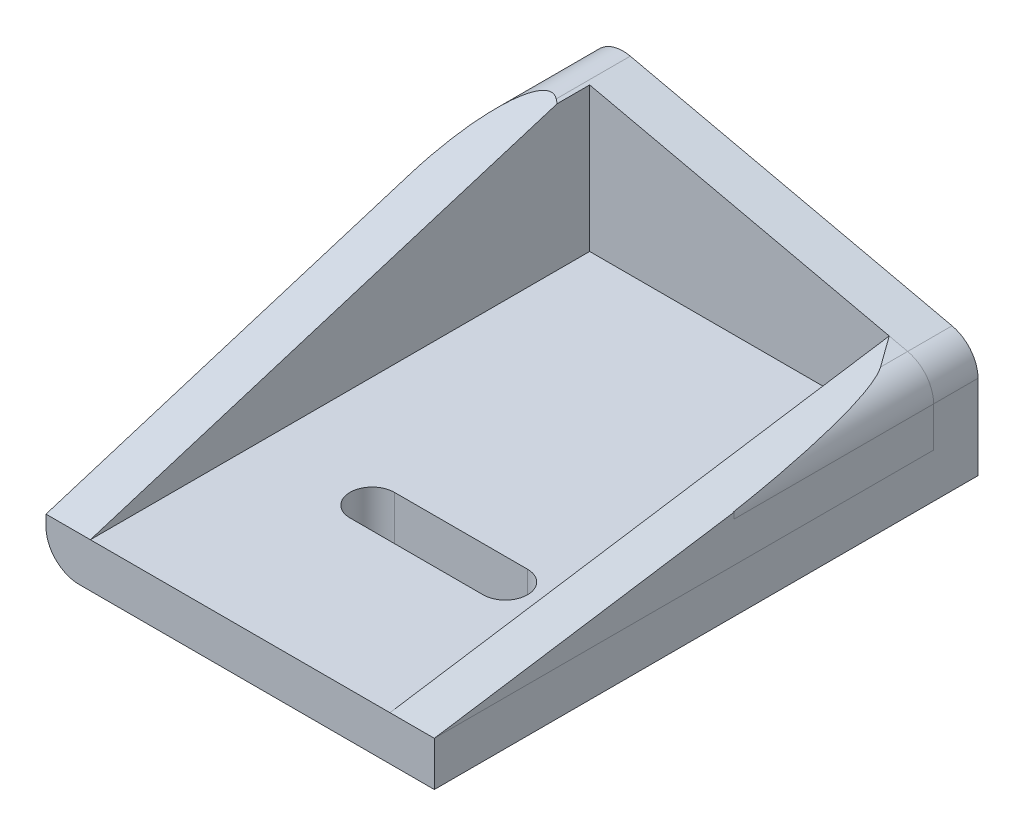
SolidWorks part; units mm, degrees
ref_plane "Front Plane" through (0, 0, 0) normal (0, 0, 1) x (1, 0, 0)
ref_plane "Top Plane" through (0, 0, 0) normal (0, 1, 0) x (1, 0, 0)
ref_plane "Right Plane" through (0, 0, 0) normal (1, 0, 0) x (0, 0, -1)
sketch "Sketch1" plane through (0, 0, 0) normal (0, 0, 1) x (1, 0, 0)
  line L1 (-155, 3) -> (-155, 7.6019) construction
  line L2 (-6, 0) -> (-152, 0) construction
  line L4 (-155, 3) -> (-155, 7.6019)
  line L5 (-120, 0) -> (-152, 0)
  line L6 (-120, 0) -> (-120, 10.5282)
  line L7 (-152, 0) -> (-155, 0)
  line L8 (-155, 0) -> (-155, 3)
  line L9 (-155, 7.6019) -> (-155, 10.5282)
  line L11 (-155, 10.5282) -> (-155, 17.9032)
  line L12 (-122.3392, 10.5282) -> (-271.3392, 44.1734) construction
  line L13 (-155, 17.9032) -> (-122.3392, 10.5282)
  line L14 (-122.3392, 10.5282) -> (-120, 10.5282)
  point P8 (-155, 5.3009)
  dimension "D1" = 35
extrude "Boss-Extrude2" add sketch "Sketch1" along normal blind 4
ref_plane "Plane2" through (-151, 0, 0) normal (-1, 0, 0) x (0, 0, 1)
sketch "Sketch6" plane through (-155, 0, 0) normal (-1, 0, 0) x (0, 0, 1)
  line L1 (4, 0) -> (49, 0)
  line L2 (4, 0) -> (4, 4)
  line L3 (4, 4) -> (49, 4)
  line L4 (49, 0) -> (49, 4)
  dimension "D1" = 4
  dimension "D2" = 45
extrude "Boss-Extrude3" add sketch "Sketch6" against normal up to surface (35 mm away) up to face at (-120, 5.2641, 2)
sketch "Sketch8" plane through (-155, 0, 0) normal (-1, 0, 0) x (0, 0, 1)
  line L0 (49, 4) -> (4, 17.9032)
  line L1 (4, 17.9032) -> (4, 4)
  line L2 (4, 4) -> (49, 4)
extrude "Boss-Extrude4" add sketch "Sketch8" against normal blind 4
ref_plane "Plane3" through (-124, 0, 0) normal (1, 0, 0) x (0, 0, -1)
sketch "Sketch9" plane through (-124, 0, 0) normal (1, 0, 0) x (0, 0, -1)
  line L0 (-4, 10.9032) -> (-49, 4)
  line L1 (-49, 4) -> (-4, 4)
  line L2 (-4, 4) -> (-4, 10.9032)
extrude "Boss-Extrude5" add sketch "Sketch9" along normal blind 4 separate body
fillet "Fillet9" radius 3 3 edges at (-155, 17.9032, 2) (-155, 0, 24.5) (-120, 10.5282, 2)
sketch "Sketch10" plane through (0, 0, 4) normal (0, 0, -1) x (-1, 0, 0)
  line L1 (120, 10.9032) -> (124, 10.9032) construction
  line L4 (120, 10.9032) -> (124, 10.9032)
  line L11 (124, 4) -> (124, 10.9032)
  line L12 (124, 10.9032) -> (120, 10.9032)
  line L13 (120, 10.9032) -> (120, 4)
  line L14 (120, 4) -> (124, 4)
  line L16 (124, 10.9032) -> (120, 10.9032)
  line L17 (120, 10.9032) -> (120, 7.6019)
  line L19 (122.3392, 10.5282) -> (124, 10.9032)
  arc A2 (122.3392, 10.5282) -> (120, 7.6019) centre (123, 7.6019) ccw construction
  arc A3 (122.3392, 10.5282) -> (120, 7.6019) centre (123, 7.6019) ccw
  line M11 (124, 10.9032) -> (120, 10.9032)
  line M12 (120, 10.9032) -> (120, 4)
  dimension "D1" = 0
extrude "Cut-Extrude4" cut sketch "Sketch10" against normal blind 18 contours A3 L19 M11 M12 region at (-121.0162, 10.2155, 4)
sketch "Sketch11" plane through (0, 0, 4) normal (0, 0, -1) x (-1, 0, 0)
  line L3 (151, 17) -> (151.3392, 17.0766)
  line L4 (151, 17.9032) -> (151, 17)
  line L5 (155, 17.9032) -> (151, 17.9032)
  line L7 (151, 17.9032) -> (151, 17)
  line L8 (155, 17.9032) -> (151, 17.9032)
  line L9 (151, 17) -> (151.3392, 17.0766)
  line L13 (155, 14.1503) -> (155, 17.9032)
  line L14 (155, 14.1503) -> (155, 17.9032)
  arc A1 (155, 14.1503) -> (151.3392, 17.0766) centre (152, 14.1503) ccw
  arc A3 (155, 14.1503) -> (151.3392, 17.0766) centre (152, 14.1503) ccw
  dimension "D1" = 0
extrude "Cut-Extrude2" cut sketch "Sketch11" against normal through all
sketch "Sketch12" plane through (0, 0, 0) normal (0, -1, 0) x (1, 0, 0)
  line L0 (-129, 33.6) -> (-141, 33.6) construction
  line L1 (-129, 31.6) -> (-141, 31.6)
  line L2 (-129, 35.6) -> (-141, 35.6)
  arc A0 (-133.25, 40.6) -> (-136.75, 40.6) centre (-135, 40.6) ccw construction
  arc A1 (-136.75, 40.6) -> (-133.25, 40.6) centre (-135, 40.6) ccw construction
  arc A2 (-133.25, 33.6) -> (-136.75, 33.6) centre (-135, 33.6) ccw construction
  arc A3 (-136.75, 33.6) -> (-133.25, 33.6) centre (-135, 33.6) ccw construction
  arc A4 (-133.25, 40.6) -> (-136.75, 40.6) centre (-135, 40.6) ccw construction
  arc A5 (-136.75, 40.6) -> (-133.25, 40.6) centre (-135, 40.6) ccw construction
  arc A6 (-133.25, 33.6) -> (-136.75, 33.6) centre (-135, 33.6) ccw construction
  arc A7 (-136.75, 33.6) -> (-133.25, 33.6) centre (-135, 33.6) ccw construction
  arc A8 (-129, 31.6) -> (-129, 35.6) centre (-129, 33.6) ccw
  arc A9 (-141, 35.6) -> (-141, 31.6) centre (-141, 33.6) ccw
  point P10 (-135, 33.6)
  dimension "D1" = 12
  dimension "D2" = 4
sketch "Sketch13" plane through (0, 0, 0) normal (0, -1, 0) x (-1, 0, 0)
  line L0 (135, -28.6) -> (135, -45.6) construction
  line L1 (121.0679, -28.6) -> (148.9321, -28.6)
  line L2 (121.0679, -28.6) -> (121.0679, -45.6)
  line L3 (121.0679, -45.6) -> (148.9321, -45.6)
  line L4 (148.9321, -28.6) -> (148.9321, -45.6) construction
  dimension "D1" = 5
  dimension "D2" = 5
extrude "Boss-Extrude6" add sketch "Sketch13" along normal blind 4.25 rebuild error yes
extrude "Cut-Extrude3" cut sketch "Sketch12" against normal through all both and the other way through all
fillet "Fillet7" radius 2 rebuild error yes
fillet "Fillet8" radius 1 rebuild error yes
